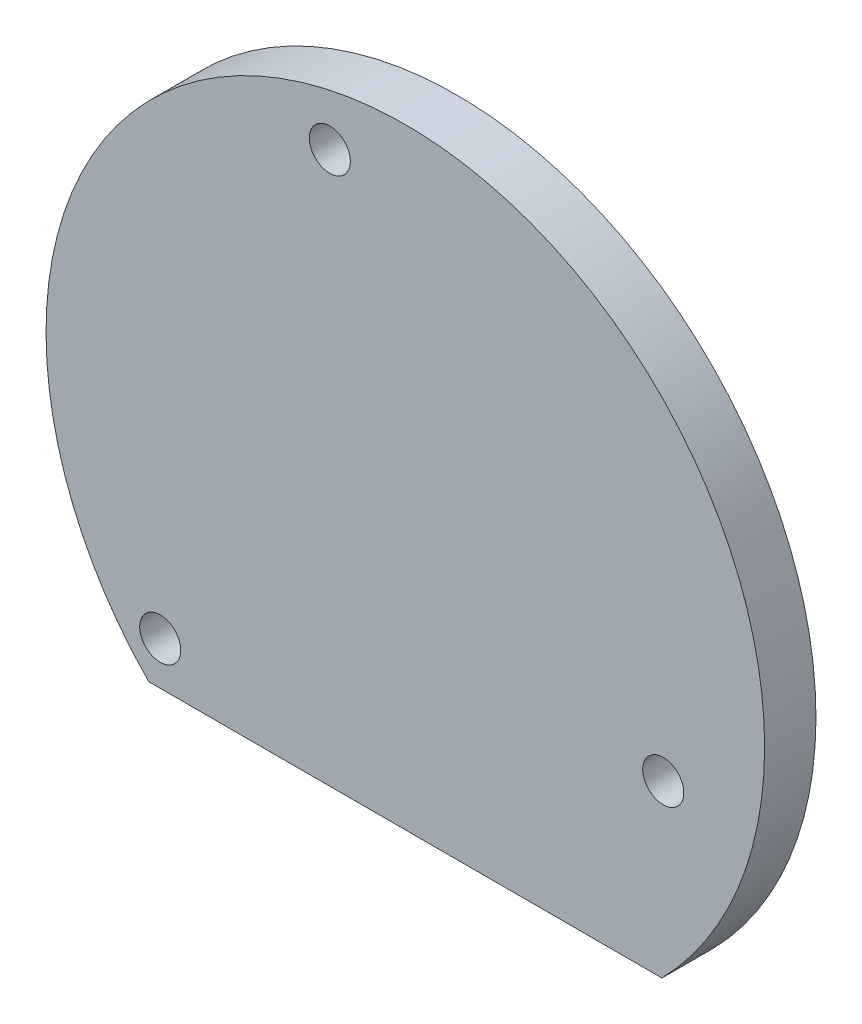
SolidWorks part; units mm, degrees
ref_plane "Front Plane" through (0, 0, 0) normal (0, 0, 1) x (1, 0, 0)
ref_plane "Top Plane" through (0, 0, 0) normal (0, 1, 0) x (1, 0, 0)
ref_plane "Right Plane" through (0, 0, 0) normal (1, 0, 0) x (0, 0, -1)
sketch "Sketch1" plane through (0, 0, 0) normal (0, 0, 1) x (1, 0, 0)
  circle A0 centre (0, 0) radius 35.56
  dimension "D1" = 71.12
extrude "Boss-Extrude1" add sketch "Sketch1" along normal blind 5.08
sketch "Sketch2" plane through (0, 0, 5.08) normal (0, 0, 1) x (1, 0, 0)
  line L0 (0, 0) -> (0, -35.56) construction
  line L6 (0, -35.56) -> (-36.2561, -35.56)
  line L7 (-36.2561, -35.56) -> (-36.2561, -24.892)
  line L8 (-36.2561, -24.892) -> (33.7504, -24.892)
  line L9 (33.7504, -24.892) -> (33.7504, -35.56)
  line L10 (33.7504, -35.56) -> (0, -35.56)
  circle A0 centre (0, 0) radius 35.56 construction
  dimension "D1" = 10.668
extrude "Cut-Extrude1" cut sketch "Sketch2" against normal through all
ref_axis "Axis1" through (0, -24.892, 0) along (0, 0, 1)
ref_plane "Plane1" through (0, 0, 0) normal (1, 0, 0) x (0, 0, 1)
sketch "Sketch7" plane through (0, 0, 5.08) normal (0, 0, 1) x (1, 0, 0)
  line L0 (-7.472, 29.6655) -> (-24.2611, -20.6265) construction
  line L1 (-7.472, 29.6655) -> (25.5229, -7.9528) construction
  line L2 (25.5229, -7.9528) -> (-24.2611, -20.6265) construction
  circle A0 centre (-24.2611, -20.6265) radius 2.032
  circle A1 centre (-7.472, 29.6655) radius 2.032
  circle A2 centre (25.5229, -7.9528) radius 2.032
  dimension "D1" = 4.064
  dimension "D2" = 50.292
  dimension "D3" = 50.038
  dimension "D4" = 49.784
extrude "Cut-Extrude2" cut sketch "Sketch7" against normal through all
equation "\"Foamcore\" = .1in"
equation "\"MDF\" = .2in"
equation "\"Gmaterial\"= \"MDF\""
equation "\"PVC-ID\" = \"1.590in\""
equation "\"PVC-OD\" = \"1.900in\""
equation "\"PVC-Sleeve-Width\" = \".51in\""
equation "\"D1@Boss-Extrude1\"=\"Gmaterial\""
